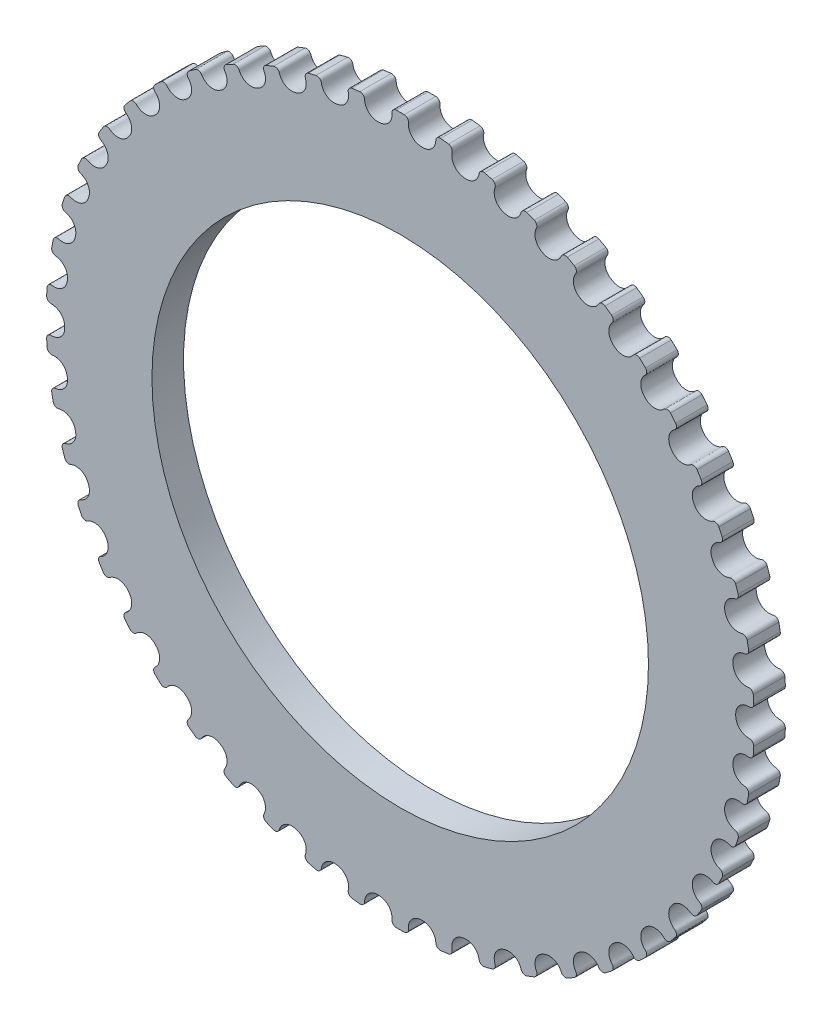
SolidWorks part; units mm, degrees
ref_plane "Front Plane" through (0, 0, 0) normal (0, 0, 1) x (1, 0, 0)
ref_plane "Top Plane" through (0, 0, 0) normal (0, 1, 0) x (1, 0, 0)
ref_plane "Right Plane" through (0, 0, 0) normal (1, 0, 0) x (0, 0, -1)
ref_axis "Axis1" through (0, 0, 55) along (0, 0, -1)
sketch "SketchRevolveGearBelt01" plane through (0, 0, 0) normal (1, 0, 0) x (0, 0, -1)
  line L0 (0, 0) -> (1, 0) construction
  line L1 (1.75, 0) -> (1.75, 39.2172)
  line L2 (1.75, 39.2172) -> (-1.75, 39.2172)
  line L3 (-1.75, 39.2172) -> (-1.75, 0)
  line L4 (-1.75, 0) -> (1.75, 0)
  dimension "GearBeltSide1" = 1.75
  dimension "GearBeltOutsideDiameter" = 39.2172
  dimension "GearBeltSide2" = 1.75
revolve "GearBelt01" add sketch "SketchRevolveGearBelt01" angle 360 about L0
sketch "SketchToothGearBelt01" plane through (0, 0, 0) normal (0, 0, 1) x (1, 0, 0)
  arc A0 (39.1647, 2.0323) -> (39.1647, -2.0323) centre (0, 0) cw
  spline S0 degree 3 poles (39.1647, -2.0323) (39.166, -2.006) (39.1649, -1.9663) (39.1569, -1.9141) (39.1478, -1.8755) (39.1356, -1.8378) (39.1204, -1.8013) (39.1023, -1.7661) (39.0814, -1.7324) (39.0578, -1.7006) (39.0317, -1.6708) (39.0033, -1.6432) (38.9728, -1.618) (38.9403, -1.5953) (38.9061, -1.5754) (38.8703, -1.5582) (38.8333, -1.5441) (38.7953, -1.533) (38.7565, -1.525) (38.7172, -1.5201) (38.6658, -1.5185) (38.59, -1.5198) (38.4897, -1.516) (38.3775, -1.5026) (38.2667, -1.4805) (38.158, -1.4498) (38.052, -1.4107) (37.9494, -1.3633) (37.8509, -1.3081) (37.7569, -1.2453) (37.6682, -1.1753) (37.5853, -1.0986) (37.5086, -1.0156) (37.4387, -0.9268) (37.376, -0.8329) (37.3208, -0.7343) (37.2735, -0.6317) (37.2344, -0.5257) (37.2037, -0.4169) (37.1817, -0.3061) (37.1683, -0.1939) (37.1652, -0.1051) (37.1655, -0.0405) (37.1655, 0) (37.1655, 0.0405) (37.1652, 0.1051) (37.1683, 0.1939) (37.1817, 0.3061) (37.2037, 0.4169) (37.2344, 0.5257) (37.2735, 0.6317) (37.3208, 0.7343) (37.376, 0.8329) (37.4387, 0.9268) (37.5086, 1.0156) (37.5853, 1.0986) (37.6682, 1.1753) (37.7569, 1.2453) (37.8509, 1.3081) (37.9494, 1.3633) (38.052, 1.4107) (38.158, 1.4498) (38.2667, 1.4805) (38.3775, 1.5026) (38.4897, 1.516) (38.59, 1.5198) (38.6658, 1.5185) (38.7172, 1.5201) (38.7565, 1.525) (38.7953, 1.533) (38.8333, 1.5441) (38.8703, 1.5582) (38.9061, 1.5754) (38.9403, 1.5953) (38.9728, 1.618) (39.0033, 1.6432) (39.0317, 1.6708) (39.0578, 1.7006) (39.0814, 1.7324) (39.1023, 1.7661) (39.1204, 1.8013) (39.1356, 1.8378) (39.1478, 1.8755) (39.1569, 1.9141) (39.1649, 1.9663) (39.166, 2.006) (39.1647, 2.0323) knots 0 0 0 0 0.012346 0.01852 0.024693 0.030866 0.037039 0.043212 0.049386 0.055559 0.061732 0.067905 0.074078 0.080252 0.086425 0.092598 0.098771 0.104944 0.111118 0.117291 0.123464 0.135171 0.152781 0.17039 0.188 0.205609 0.223219 0.240828 0.258438 0.276048 0.293657 0.311267 0.328876 0.346486 0.364095 0.381705 0.399315 0.416924 0.434534 0.452143 0.469753 0.487362 0.493681 0.5 0.506319 0.512638 0.530247 0.547857 0.565466 0.583076 0.600685 0.618295 0.635905 0.653514 0.671124 0.688733 0.706343 0.723952 0.741562 0.759172 0.776781 0.794391 0.812 0.82961 0.847219 0.864829 0.876536 0.882709 0.888882 0.895056 0.901229 0.907402 0.913575 0.919748 0.925922 0.932095 0.938268 0.944441 0.950614 0.956788 0.962961 0.969134 0.975307 0.98148 0.987654 1 1 1 1
extrude "ToothExtrudeCutGearBelt01" cut sketch "SketchToothGearBelt01" against normal blind 7.239 and the other way blind 7.239
pattern_circular "PatternGearBelt01" count 50 every 7.2 about axis through (0, 0, 55) along (0, 0, -1) of "ToothExtrudeCutGearBelt01"
sketch "BoreRevolveSketch" plane through (0, 0, 0) normal (1, 0, 0) x (0, 0, -1)
  line L0 (0, 0) -> (1, 0) construction
  line L1 (-7.239, 0) -> (7.239, 0)
  line L2 (7.239, 0) -> (7.239, 27.5)
  line L3 (7.239, 27.5) -> (-7.239, 27.5)
  line L4 (-7.239, 27.5) -> (-7.239, 0)
  dimension "BoreSide1" = 7.239
  dimension "TaperSide1" = 27.5
  dimension "BoreSide2" = 7.239
  dimension "TaperSide2" = 27.5
revolve "BoreRevolveCut" cut sketch "BoreRevolveSketch" angle 360 about L0
sketch "AuxiliarySketchGearBelt01" plane through (0, 0, 0) normal (0, 0, 1) x (1, 0, 0)
  circle A0 centre (0, 0) radius 39.7887 construction
  dimension "PitchDiameter" = 79.5774
